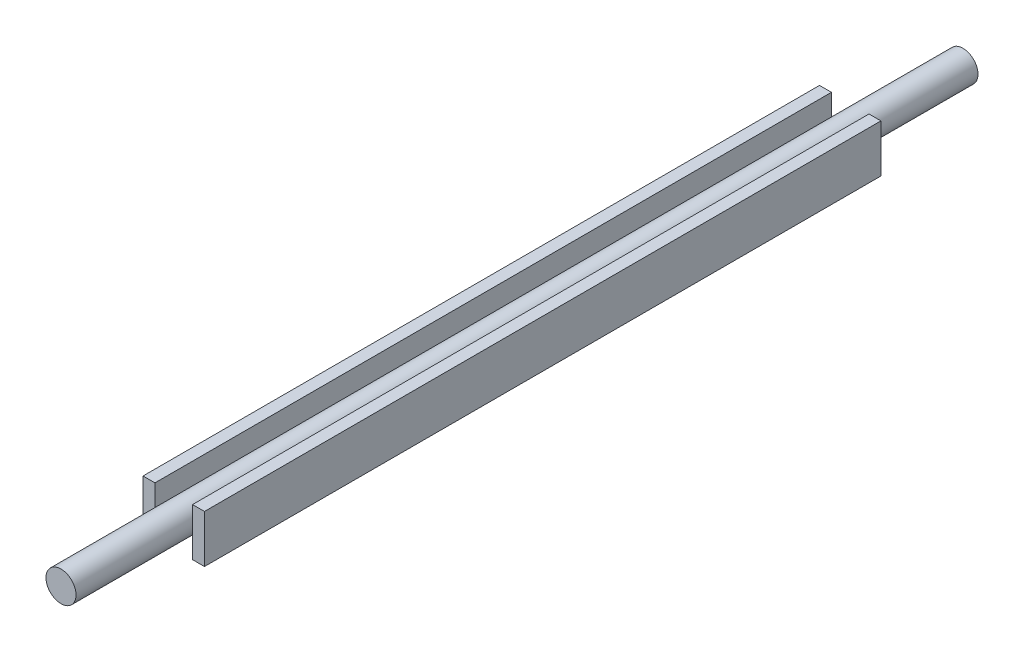
SolidWorks part; units mm, degrees
ref_plane "Front Plane" through (0, 0, 0) normal (0, 0, 1) x (1, 0, 0)
ref_plane "Top Plane" through (0, 0, 0) normal (0, 1, 0) x (1, 0, 0)
ref_plane "Right Plane" through (0, 0, 0) normal (1, 0, 0) x (0, 0, -1)
sketch "Sketch1" plane through (0, 0, 0) normal (0, 0, 1) x (1, 0, 0)
  line L0 (0, 0) -> (0, 67.0118) construction
  line L1 (-6.5875, 0) -> (6.5875, 0) construction
  line L2 (8.175, -6.35) -> (5, -6.35)
  line L3 (-8.175, 6.35) -> (-5, 6.35)
  line L4 (-8.175, 6.35) -> (-8.175, -6.35)
  line L5 (-8.175, -6.35) -> (-5, -6.35)
  line L6 (-5, 6.35) -> (-5, -6.35)
  line L7 (-8.175, 6.35) -> (-5, -6.35) construction
  line L8 (-8.175, -6.35) -> (-5, 6.35) construction
  line L9 (5, 6.35) -> (5, -6.35)
  line L10 (8.175, 6.35) -> (5, 6.35)
  line L11 (8.175, 6.35) -> (8.175, -6.35)
  circle A0 centre (0, 0) radius 4
  point P14 (25.9321, 0)
  point P15 (-10.4384, 0)
  dimension "D1" = 8
  dimension "D2" = 12.7
  dimension "D3" = 3.175
  dimension "D4" = 1
extrude "Boss-Extrude1" add sketch "Sketch1" along normal mid plane 180 contours L11 L10 L9 L2 | L6 L3 L4 L5 region at (6.5875, 0, 0) region at (-6.5875, 0, 0)
extrude "Boss-Extrude2" add sketch "Sketch1<3>" along normal mid plane 240 separate body contours A0
sketch "Sketch1<3>" plane through (0, 0, 0) normal (0, 0, 1) x (1, 0, 0) same geometry as "Sketch1"
sketch "Sketch2" plane through (0, 0, 90) normal (0, 0, 1) x (1, 0, 0)
  line L0 (0, 0) -> (0, 8.6431) construction
  line L1 (5, 6.35) -> (5, -6.35)
  line L2 (5, -6.35) -> (0.3085, -6.35)
  line L3 (0.3085, -6.35) -> (0.3085, -3.9881)
  line L4 (0.3085, 3.9881) -> (0.3085, 6.35)
  line L5 (0.3085, 6.35) -> (5, 6.35)
  circle A0 centre (0, 0) radius 4 construction
  circle A1 centre (0, 0) radius 4
